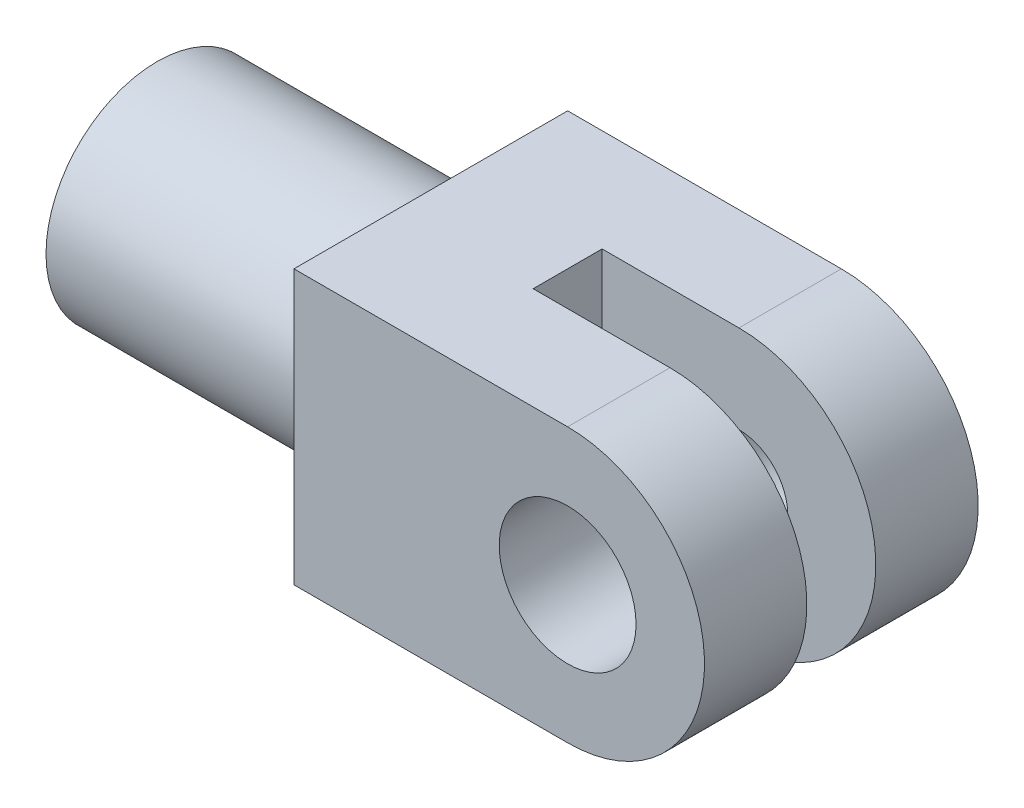
SolidWorks part; units mm, degrees
material "Free-Cutting Brass, UNS C36000"
ref_plane "Front Plane" through (0, 0, 0) normal (0, 0, 1) x (1, 0, 0)
ref_plane "Top Plane" through (0, 0, 0) normal (0, 1, 0) x (1, 0, 0)
ref_plane "Right Plane" through (0, 0, 0) normal (1, 0, 0) x (0, 0, -1)
sketch "Sketch2" plane through (0, 0, 0) normal (0, 0, 1) x (1, 0, 0)
  line L0 (0, 3.175) -> (0, -3.175) construction
  line L5 (-6.35, 3.175) -> (0, 3.175)
  line L6 (-6.35, 3.175) -> (-6.35, -3.175)
  line L7 (-6.35, -3.175) -> (0, -3.175)
  line L9 (-6.35, 3.175) -> (0, 0) construction
  line L10 (-6.35, -3.175) -> (0, 0) construction
  arc A0 (0, 3.175) -> (0, -3.175) centre (0, 0) cw
  point P0 (0, 0)
  dimension "D3" = 3.175
  dimension "D1" = 6.35
  dimension "D2" = 6.35
extrude "Boss-Extrude2" add sketch "Sketch2" along normal mid plane 6.35
ref_plane "Plane1" through (3.175, 0, 0) normal (1, 0, 0) x (0, 0, -1)
sketch "Sketch3" plane through (3.175, 0, 0) normal (1, 0, 0) x (0, 0, -1)
  line L0 (-3.175, -3.175) -> (3.175, -3.175) construction
  line L1 (-0.8001, 3.175) -> (0.8001, 3.175)
  line L2 (-0.8001, 3.175) -> (-0.8001, -3.175)
  line L3 (-0.8001, -3.175) -> (0.8001, -3.175)
  line L4 (0.8001, 3.175) -> (0.8001, -3.175)
  line L5 (-0.8001, 3.175) -> (0.8001, -3.175) construction
  line L6 (-0.8001, -3.175) -> (0.8001, 3.175) construction
  point P0 (0, 0)
  dimension "D1" = 1.6002
extrude "Cut-Extrude1" cut sketch "Sketch3" against normal blind 6.35
sketch "Sketch4" plane through (-6.35, 0, 0) normal (-1, 0, 0) x (0, 0, 1)
  circle A0 centre (0, 0) radius 2.5781
  dimension "D1" = 5.1562
extrude "Boss-Extrude3" add sketch "Sketch4" along normal blind 6.35
hole_wizard "#5-40 Tapped Hole1" positions "Sketch5" profile "Sketch6" tap size "#5-40" standard "ANSI Inch"
sketch "Sketch5" plane through (-12.7, 0, 0) normal (-1, 0, 0) x (0, 0, 1)
  point P0 (0, 0)
sketch "Sketch6" plane through (-12.7, 0, 0) normal (0, 1, 0) x (0, 0, 1)
  line L0 (0, 0) -> (0, 10.2995)
  line L1 (0, 10.2995) -> (1.289, 9.525)
  line L2 (1.289, 9.525) -> (1.289, 0)
  line L5 (1.289, 0) -> (0, 0)
  line L10 (0, 10.2995) -> (-1.2891, 9.525) construction
  line L11 (0, -6.35) -> (0, 107.95) construction
  dimension "Tap Drill Dia." = 2.5781
  dimension "Tap Drill Depth" = 9.525
  dimension "Drill Angle" = 118
cosmetic thread "Hole Thread1" parameters "D1"=6.35, "D2"=3.175
hole_wizard "1/8 (0.125) Diameter Hole1" positions "Sketch9" profile "Sketch8" hole size "1/8" standard "ANSI Inch" end condition up to next
sketch "Sketch9" plane through (0, 0, 3.175) normal (0, 0, 1) x (1, 0, 0)
  point P0 (0, 0)
sketch "Sketch8" plane through (0, 0, 3.175) normal (1, 0, 0) x (0, -1, 0)
  line L0 (0, 0) -> (0, 2.3749)
  line L1 (0, 2.3749) -> (1.5875, 2.3749)
  line L2 (1.5875, 2.3749) -> (1.5875, 0)
  line L5 (1.5875, 0) -> (0, 0)
  line L11 (0, -6.35) -> (0, 107.95) construction
  dimension "Thru Hole Dia." = 3.175
  dimension "Thru Hole Depth" = 2.3749
hole_wizard "#4-40 Tapped Hole1" positions "Sketch10" profile "Sketch11" tap size "#4-40" standard "ANSI Inch" end condition through all
sketch "Sketch10" plane through (0, 0, -0.8001) normal (0, 0, 1) x (1, 0, 0)
  point P0 (0, 0)
sketch "Sketch11" plane through (0, 0, -0.8001) normal (1, 0, 0) x (0, -1, 0)
  line L0 (0, 0) -> (0, 2.3749)
  line L1 (0, 2.3749) -> (1.1303, 2.3749)
  line L2 (1.1303, 2.3749) -> (1.1303, 0)
  line L5 (1.1303, 0) -> (0, 0)
  line L11 (0, -6.35) -> (0, 107.95) construction
  dimension "Thru Tap Drill Dia." = 2.2606
  dimension "Thru Tap Drill Depth" = 2.3749
cosmetic thread "Hole Thread2" parameters "D2"=2.8448
